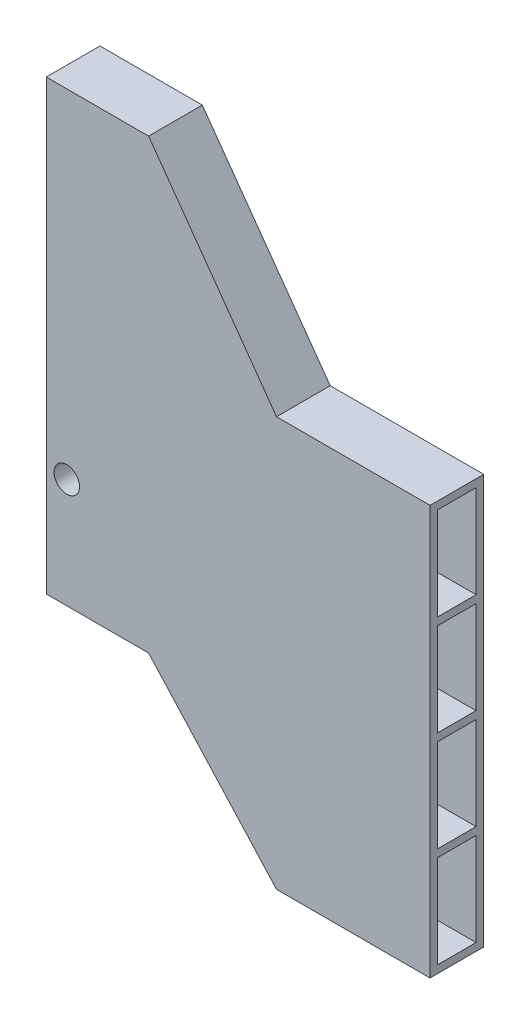
SolidWorks part; units mm, degrees
material "ABS"
ref_plane "Front Plane" through (0, 0, 0) normal (0, 0, 1) x (1, 0, 0)
ref_plane "Top Plane" through (0, 0, 0) normal (0, 1, 0) x (1, 0, 0)
ref_plane "Right Plane" through (0, 0, 0) normal (1, 0, 0) x (0, 0, -1)
sketch "Sketch1" plane through (0, 0, 0) normal (0, 0, 1) x (1, 0, 0)
  line L0 (0, 0) -> (0, 87.5)
  line L1 (0, 87.5) -> (20, 87.5)
  line L2 (20, 87.5) -> (20, 0) construction
  line L3 (20, 0) -> (0, 0)
  line L4 (0, 37.575) -> (20, 41.3)
  line L5 (0, 5.225) -> (20, 1.5)
  line L6 (0, 15.225) -> (20, 18.95)
  line L7 (0, 10.225) -> (20, 10.225) construction
  line L8 (0, 27.575) -> (20, 23.85)
  line L9 (0, 59.925) -> (20, 63.65)
  line L10 (0, 49.925) -> (20, 46.2)
  line L11 (0, 82.275) -> (20, 86)
  line L12 (0, 72.275) -> (20, 68.55)
  line L13 (0, 15.225) -> (0, 37.575) construction
  line L14 (0, 43.75) -> (20, 43.75) construction
  line L15 (10, 48.0625) -> (10, 39.4375) construction
  line L16 (20, 87.5) -> (45, 52.5)
  line L17 (45, 52.5) -> (45, -27.5) construction
  line L18 (45, -27.5) -> (20, 0)
  line L19 (20, 1.5) -> (45, -26)
  line L20 (20, 18.95) -> (45, -7.875)
  line L21 (20, 23.85) -> (45, -6.375)
  line L22 (20, 41.3) -> (45, 11.75)
  line L23 (20, 46.2) -> (45, 13.25)
  line L24 (20, 63.65) -> (45, 31.375)
  line L25 (20, 68.55) -> (45, 32.875)
  line L26 (20, 86) -> (45, 51)
  line L27 (45, -7.875) -> (45, -26) construction
  line L28 (45, -26) -> (45, -27.5) construction
  line L29 (45, -7.875) -> (45, -6.375) construction
  line L30 (45, -6.375) -> (45, 11.75) construction
  line L31 (45, 11.75) -> (45, 13.25) construction
  line L32 (45, 13.25) -> (45, 31.375) construction
  line L33 (45, 31.375) -> (45, 32.875) construction
  line L34 (45, 32.875) -> (45, 51) construction
  line L35 (45, 51) -> (45, 52.5) construction
  line L36 (20, 21.4) -> (0, 21.4) construction
  line L37 (20, 23.85) -> (20, 18.95) construction
  line L38 (45, 52.5) -> (75, 52.5)
  line L39 (75, 52.5) -> (75, -27.5)
  line L40 (75, -27.5) -> (45, -27.5)
  line L41 (45, -26) -> (75, -26)
  line L42 (45, -7.875) -> (75, -7.875)
  line L43 (45, -6.375) -> (75, -6.375)
  line L44 (45, 11.75) -> (75, 11.75)
  line L45 (45, 13.25) -> (75, 13.25)
  line L46 (45, 31.375) -> (75, 31.375)
  line L47 (45, 32.875) -> (75, 32.875)
  line L48 (45, 51) -> (75, 51)
  circle A0 centre (4, 21.4) radius 2.5
  point P28 (10, 43.75)
  dimension "D12" = 5
  dimension "D1" = 87.5
  dimension "D2" = 10
  dimension "D3" = 1.5
  dimension "D4" = 4
  dimension "D5" = 20
  dimension "D6" = 22.35
  dimension "D7" = 35
  dimension "D8" = 45
  dimension "D9" = 80
  dimension "D10" = 1.5
  dimension "D11" = 4
  dimension "D13" = 75
extrude "Boss-Extrude1" add sketch "Sketch1" against normal blind 1.5 contours L26 L48 L39 L38 L16 L1 L0 L11 | L48 L26 L11 L0 L12 L25 L47 L39 | L47 L25 L12 L0 L9 L24 L46 L39 | L46 L24 L9 L0 L10 L23 L45 L39 | L45 L23 L10 L0 L4 L22 L44 L39 | L44 L22 L4 L0 L8 L21 L43 L39 | L43 L21 L8 L0 L6 L20 L42 L39 A0 | L42 L20 L6 L0 L5 L19 L41 L39 | L41 L19 L5 L0 L3 L18 L40 L39 region at (29.8303, -10.4616, 0) region at (39.674, -6.2819, 0) region at (0.8296, 21.4, 0) region at (39.674, 14.4121, 0) region at (0.8416, 43.75, 0) region at (39.674, 35.1061, 0) region at (0.8543, 66.1, 0) region at (39.674, 55.8, 0) region at (0.8341, 84.8875, 0)
extrude "Boss-Extrude2" add sketch "Sketch1<13>" along normal blind 7.5 contours L26 L48 L39 L38 L16 L1 L0 L11 | L47 L25 L12 L0 L9 L24 L46 L39 | L45 L23 L10 L0 L4 L22 L44 L39 | L43 L21 L8 L0 L6 L20 L42 L39 A0 | L41 L19 L5 L0 L3 L18 L40 L39 region at (29.8303, -10.4616, 0) region at (0.8296, 21.4, 0) region at (0.8416, 43.75, 0) region at (0.8543, 66.1, 0) region at (0.8341, 84.8875, 0)
sketch "Sketch1<13>" plane through (0, 0, 0) normal (0, 0, 1) x (1, 0, 0) same geometry as "Sketch1"
extrude "Boss-Extrude3" add sketch "Sketch1<14>" along normal blind 1.5 from offset 7.5 contours L41 L19 L5 L0 L3 L18 L40 L39 | L42 L20 L6 L0 L5 L19 L41 L39 | L43 L21 L8 L0 L6 L20 L42 L39 A0 | L44 L22 L4 L0 L8 L21 L43 L39 | L45 L23 L10 L0 L4 L22 L44 L39 | L46 L24 L9 L0 L10 L23 L45 L39 | L47 L25 L12 L0 L9 L24 L46 L39 | L48 L26 L11 L0 L12 L25 L47 L39 | L26 L48 L39 L38 L16 L1 L0 L11 region at (29.8303, -10.4616, 0) region at (39.674, -6.2819, 0) region at (0.8296, 21.4, 0) region at (39.674, 14.4121, 0) region at (0.8416, 43.75, 0) region at (39.674, 35.1061, 0) region at (0.8543, 66.1, 0) region at (39.674, 55.8, 0) region at (0.8341, 84.8875, 0)
sketch "Sketch1<14>" plane through (0, 0, 0) normal (0, 0, 1) x (1, 0, 0) same geometry as "Sketch1"
